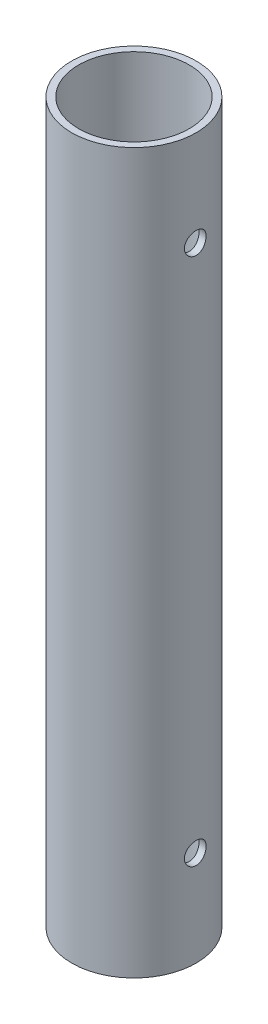
SolidWorks part; units mm, degrees
ref_plane "Front Plane" through (0, 0, 0) normal (0, 0, 1) x (1, 0, 0)
ref_plane "Top Plane" through (0, 0, 0) normal (0, 1, 0) x (1, 0, 0)
ref_plane "Right Plane" through (0, 0, 0) normal (1, 0, 0) x (0, 0, -1)
sketch "Sketch1" plane through (0, 0, 0) normal (0, 1, 0) x (1, 0, 0)
  circle A0 centre (0, 0) radius 14.2875
  circle A1 centre (0, 0) radius 12.7
  dimension "D1" = 28.575
  dimension "D2" = 1.5875
extrude "Boss-Extrude1" add sketch "Sketch1" along normal mid plane 165.1
sketch "Sketch2" plane through (0, 0, 0) normal (1, 0, 0) x (0, 0, -1)
  line L0 (14.2875, 82.55) -> (-14.2875, 82.55) construction
  circle A0 centre (0, 60.6425) radius 2.4892
  dimension "D1" = 4.9784
  dimension "D2" = 21.9075
extrude "Cut-Extrude1" cut sketch "Sketch2" against normal through all both and the other way through all
mirror "Mirror1" about plane through (0, 0, 0) normal (0, 1, 0) of "Cut-Extrude1"
